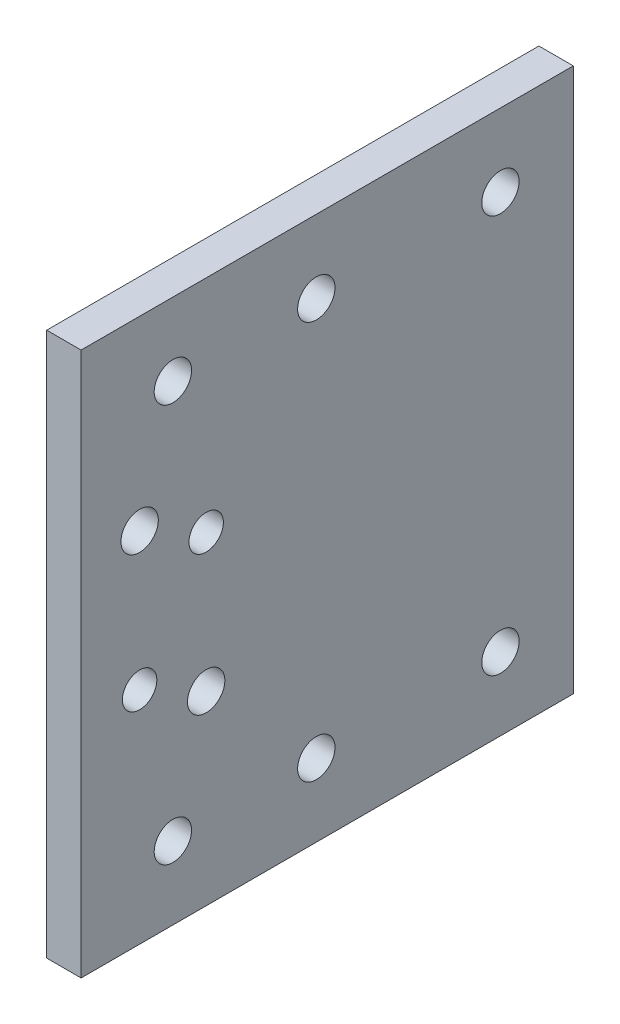
SolidWorks part; units mm, degrees
ref_plane "Front Plane" through (0, 0, 0) normal (1, 0, 0) x (0, 1, 0)
ref_plane "Top Plane" through (0, 0, 0) normal (0, 0, 1) x (0, 1, 0)
ref_plane "Right Plane" through (0, 0, 0) normal (0, 1, 0) x (-1, 0, 0)
sketch "Sketch1" plane through (0, 0, 0) normal (1, 0, 0) x (0, 1, 0)
  line L0 (0, 25) -> (0, -25) construction
  line L1 (-47.4, -25) -> (47.4, -25) construction
  line L2 (-47.4, -25) -> (-47.4, 25) construction
  line L3 (-47.4, 25) -> (47.4, 25) construction
  line L4 (47.4, -25) -> (47.4, 25) construction
  line L5 (-47.4, -25) -> (47.4, 25) construction
  line L6 (-47.4, 25) -> (47.4, -25) construction
  line L13 (-9, 5.8) -> (9, -5.8) construction
  line L14 (-34.7, -15) -> (34.7, -15) construction
  line L15 (-34.7, -15) -> (-34.7, 15) construction
  line L16 (-34.7, 15) -> (34.7, 15) construction
  line L17 (34.7, -15) -> (34.7, 15) construction
  line L18 (-34.7, -15) -> (34.7, 15) construction
  line L19 (-34.7, 15) -> (34.7, -15) construction
  line L20 (-47.4, -25) -> (47.4, -25) construction
  line L21 (-47.4, -25) -> (-47.4, -69.8)
  line L22 (-47.4, -69.8) -> (47.4, -69.8)
  line L23 (47.4, -25) -> (47.4, -69.8) construction
  line L24 (-47.4, -69.8) -> (-34.7, -69.8) construction
  line L25 (-47.4, -69.8) -> (-47.4, -57.1) construction
  line L26 (-47.4, -57.1) -> (-34.7, -57.1) construction
  line L27 (-34.7, -69.8) -> (-34.7, -57.1) construction
  line L28 (47.4, -69.8) -> (34.7, -69.8) construction
  line L29 (47.4, -69.8) -> (47.4, -57.1) construction
  line L30 (47.4, -57.1) -> (34.7, -57.1) construction
  line L31 (34.7, -69.8) -> (34.7, -57.1) construction
  line L34 (47.4, -69.8) -> (47.4, 16)
  line L40 (-47.4, -25) -> (-47.4, 16)
  line L43 (-47.4, 16) -> (47.4, 16)
  line L44 (-47.4, -44.4) -> (47.4, -44.4) construction
  circle A0 centre (-9, 5.8) radius 3
  circle A1 centre (-15, -5.8) radius 3.2576
  circle A2 centre (9, -5.8) radius 3
  circle A3 centre (15, 5.8) radius 3.2576
  circle A4 centre (-34.7, 15) radius 2.555 construction
  circle A5 centre (-34.7, -15) radius 2.555 construction
  circle A6 centre (34.7, 15) radius 2.555 construction
  circle A7 centre (34.7, -15) radius 2.555 construction
  circle A8 centre (-34.7, -57.1) radius 3.2576
  circle A9 centre (34.7, -57.1) radius 3.2576
  circle A10 centre (-34.7, -25) radius 3.2576
  circle A11 centre (-34.7, 0) radius 3.2576
  circle A12 centre (34.7, 0) radius 3.2576
  circle A13 centre (34.7, -25) radius 3.2576
  point P0 (0, 0)
  point P8 (0, 0)
  point P17 (0, 0)
  point P48 (0, 0)
  point P49 (0, 0)
  point P50 (0, 0)
  point P51 (0, 0)
  point P52 (0, 0)
  dimension "D9" = 5.11
  dimension "D10" = 5.11
  dimension "D12" = 6
  dimension "D13" = 6
  dimension "D17" = 6.5151
  dimension "D5" = 6.5151
  dimension "D2" = 24
  dimension "D3" = 94.8
  dimension "D4" = 50
  dimension "D8" = 30
  dimension "D15" = 12.7
  dimension "D16" = 12.7
  dimension "D7" = 12.7
  dimension "D19" = 25.4
  dimension "D14" = 38.6
  dimension "D20" = 10.2
  dimension "D6" = 5.8
  dimension "D11" = 9
  dimension "D18" = 5.8
  dimension "D21" = 24
extrude "Boss-Extrude1" add sketch "Sketch1" along normal blind 6
equation "\"D18@Sketch1\"=\"D6@Sketch1\""
equation "\"D21@Sketch1\"=\"D2@Sketch1\""
